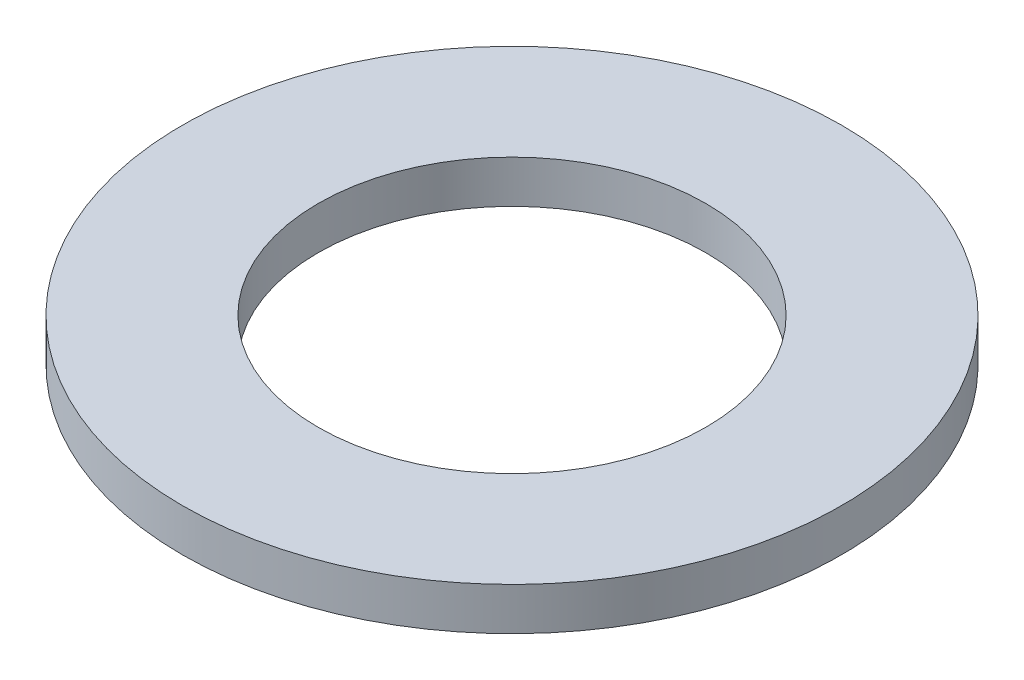
SolidWorks part; units mm, degrees
ref_plane "Front Plane" through (0, 0, 0) normal (0, 0, 1) x (1, 0, 0)
ref_plane "Top Plane" through (0, 0, 0) normal (0, 1, 0) x (1, 0, 0)
ref_plane "Right Plane" through (0, 0, 0) normal (1, 0, 0) x (0, 0, -1)
sketch "Sketch1" plane through (0, 0, 0) normal (0, 1, 0) x (1, 0, 0)
  circle A0 centre (0, 0) radius 85
  dimension "FLANGE_OD" = 170
extrude "Boss-Extrude1" add sketch "Sketch1" along normal blind 11
sketch "Sketch2" plane through (0, 0, 0) normal (0, 1, 0) x (1, 0, 0)
  circle A0 centre (0, 0) radius 50
  dimension "BORE_D" = 100
extrude "Cut-Extrude1" cut sketch "Sketch2" along normal through all
sketch "Sketch3" plane through (0, 11, 0) normal (0, 1, 0) x (1, 0, 0)
  circle A0 centre (0, 0) radius 34.3236 construction
  circle A1 centre (-34.3236, 0) radius 1.6127
  dimension "BOLT_D" = 3.2255
  dimension "BOLT_PCD" = 68.6472
extrude "Cut-Extrude2" cut sketch "Sketch3" against normal blind 8.9954 rebuild error yes
pattern_circular "CirPattern1" count 8 over 360 rebuild error yes
